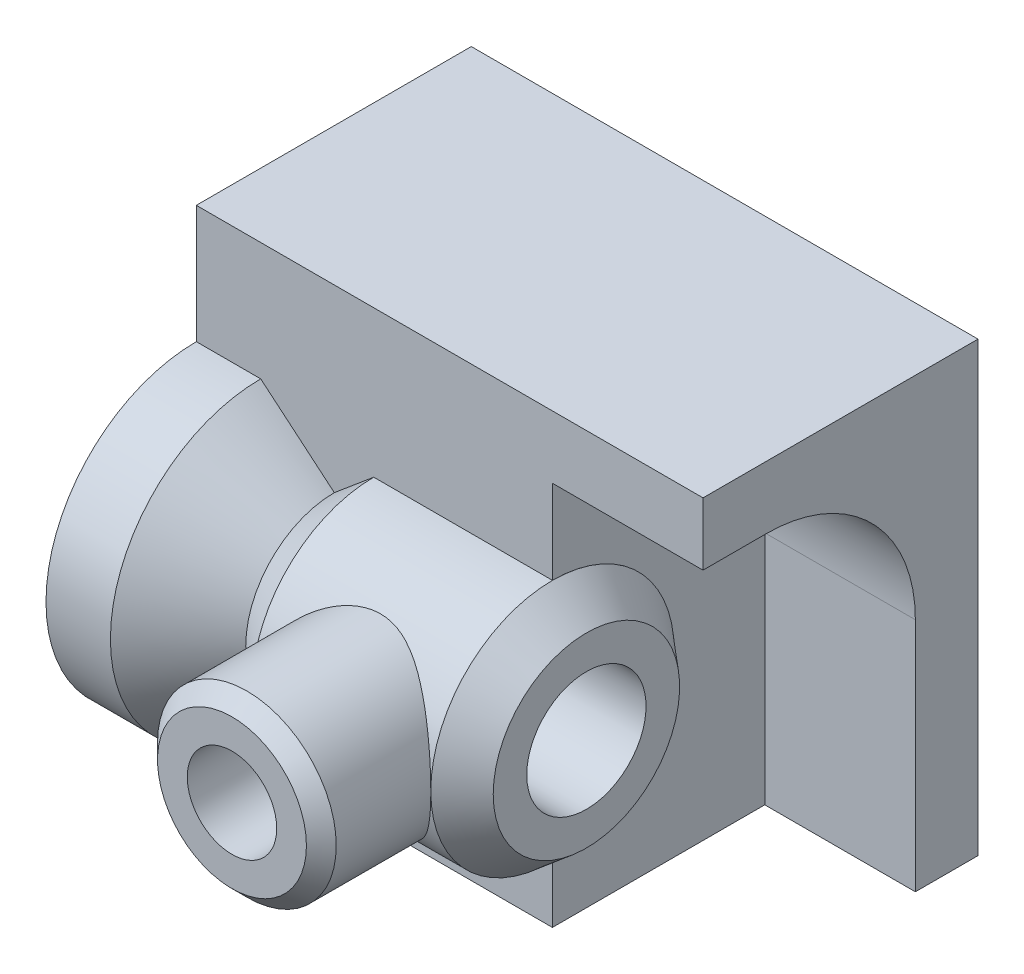
SolidWorks part; units mm, degrees
ref_plane "Front Plane" through (0, 0, 0) normal (0, 0, 1) x (1, 0, 0)
ref_plane "Top Plane" through (0, 0, 0) normal (0, 1, 0) x (1, 0, 0)
ref_plane "Right Plane" through (0, 0, 0) normal (1, 0, 0) x (0, 0, -1)
sketch "Sketch1" plane through (0, 0, 0) normal (0, 0, 1) x (1, 0, 0)
  line L0 (-0.1637, 0) -> (6.6265, 0) construction
  line L1 (0, 3.65) -> (3, 3.65)
  line L2 (3, 3.65) -> (3, 2)
  line L3 (3, 2) -> (13.08, 2)
  line L4 (13.08, 2) -> (13.08, 3.125)
  line L5 (13.08, 3.125) -> (11.9419, 4.08)
  line L6 (11.9419, 4.08) -> (5.9498, 4.08)
  line L7 (5.9498, 4.08) -> (4.6269, 2.97)
  line L8 (4.6269, 2.97) -> (2.16, 5.04)
  line L9 (2.16, 5.04) -> (0, 5.04)
  line L10 (0, 5.04) -> (0, 3.65)
  point P7 (0, 0)
  point P14 (10.3129, 3.3298)
  point P17 (0, 0)
  point P18 (0, 0)
  dimension "D1" = 3.65
  dimension "D2" = 2
  dimension "D3" = 140
  dimension "D4" = 13.08
  dimension "D5" = 4.08
  dimension "D6" = 5.04
  dimension "D7" = 3
  dimension "D8" = 2.16
  dimension "D9" = 2.97
  dimension "D10" = 3.125
  dimension "D11" = 140
  dimension "D12" = 140
revolve "Revolve1" add sketch "Sketch1" angle 360 about L0
sketch "Sketch2" plane through (0, 0, 0) normal (0, 0, 1) x (1, 0, 0)
  line L0 (11.9419, 4.08) -> (11.9419, -4.08) construction
  line L1 (5.9498, 4.08) -> (5.9498, -4.08) construction
  circle A0 centre (8.9458, 0) radius 2.996
  point P2 (0, 0)
extrude "Boss-Extrude1" add sketch "Sketch2" along normal blind 7.75
sketch "Sketch3" plane through (0, 0, 0) normal (-1, 0, 0) x (0, 0, 1)
  line L1 (-9.22, 9) -> (0, 9)
  line L2 (-9.22, 9) -> (-9.22, -6)
  line L3 (-9.22, -6) -> (0, -6)
  line L4 (0, 9) -> (0, -6)
  circle A1 centre (0, 0) radius 5.04 construction
  dimension "D3" = 9
  dimension "D1" = 15
  dimension "D2" = 9.22
extrude "Boss-Extrude2" add sketch "Sketch3" against normal blind 11.94
sketch "Sketch4" plane through (11.94, 0, 0) normal (1, 0, 0) x (0, 0, -1)
  line L0 (0, 9) -> (9.22, 9) construction
  line L1 (9.22, 9) -> (9.22, -6) construction
  line L2 (0, 9) -> (9.22, 9)
  line L3 (9.22, 9) -> (9.22, -6)
  line L4 (0, 9) -> (0, 6.9)
  line L5 (0, 4.08) -> (0, 9) construction
  line L6 (0, 6.9) -> (7.12, 6.9)
  line L7 (7.12, 6.9) -> (7.12, -6)
  line L8 (9.22, -6) -> (0, -6) construction
  line L9 (7.12, -6) -> (9.22, -6)
  dimension "D1" = 2.1
  dimension "D2" = 2.1
extrude "Boss-Extrude3" add sketch "Sketch4" along normal blind 5.05
fillet "Fillet1" radius 5 1 edges at (14.465, 6.9, -7.12)
chamfer "Chamfer1" distance 0.5 angle 45 1 edges at (11.9419, 0, 7.75)
sketch "Sketch5" plane through (0, 0, 7.75) normal (0, 0, 1) x (1, 0, 0)
  circle A0 centre (8.9458, 0) radius 1.5
  dimension "D1" = 3
extrude "Cut-Extrude1" cut sketch "Sketch5" against normal up to surface (7.75 mm away) up to face at (11.8128, 0.7373, 0)
sketch "Sketch6" plane through (13.08, 0, 0) normal (1, 0, 0) x (0, 0, -1)
  circle A0 centre (0, 0) radius 2 construction
  circle A1 centre (0, 0) radius 2
extrude "Cut-Extrude2" cut sketch "Sketch6" against normal up to surface (13.08 mm away) up to face at (0, 0, 1.825)
sketch "Sketch7" plane through (0, 0, 0) normal (-1, 0, 0) x (0, 0, 1)
  circle A0 centre (0, 0) radius 3.65
extrude "Cut-Extrude3" cut sketch "Sketch7" against normal up to surface (3 mm away) up to face at (3, 0, 1.4125)
